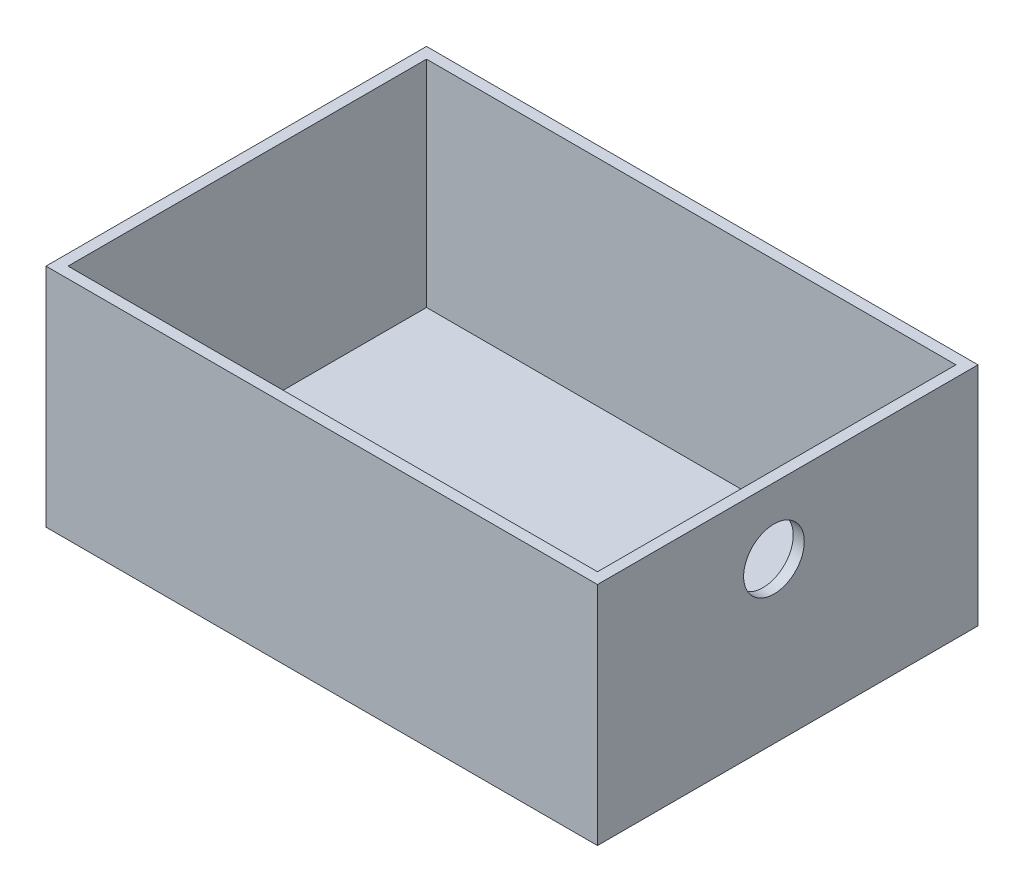
SolidWorks part; units mm, degrees
ref_plane "Front Plane" through (0, 0, 0) normal (0, 0, 1) x (1, 0, 0)
ref_plane "Top Plane" through (0, 0, 0) normal (0, 1, 0) x (1, 0, 0)
ref_plane "Right Plane" through (0, 0, 0) normal (1, 0, 0) x (0, 0, -1)
sketch "Sketch1" plane through (0, 0, 0) normal (0, 1, 0) x (1, 0, 0)
  line L1 (-50, -34.5) -> (50, -34.5)
  line L2 (-50, -34.5) -> (-50, 34.5)
  line L3 (-50, 34.5) -> (50, 34.5)
  line L4 (50, -34.5) -> (50, 34.5)
  line L5 (-50, -34.5) -> (50, 34.5) construction
  line L6 (-50, 34.5) -> (50, -34.5) construction
  point P0 (0, 0)
  dimension "D1" = 100
  dimension "D2" = 69
extrude "Boss-Extrude1" add sketch "Sketch1" along normal blind 41 contours L4 L3 L2 L1
sketch "Sketch3" plane through (0, 41, 0) normal (0, 1, 0) x (1, 0, 0)
  line L1 (-48, -32.5) -> (48, -32.5)
  line L2 (-48, -32.5) -> (-48, 32.5)
  line L3 (-48, 32.5) -> (48, 32.5)
  line L4 (48, -32.5) -> (48, 32.5)
  line L5 (-48, -32.5) -> (48, 32.5) construction
  line L6 (-48, 32.5) -> (48, -32.5) construction
  point P0 (0, 0)
  dimension "D1" = 96
  dimension "D2" = 65
extrude "Cut-Extrude2" cut sketch "Sketch3" against normal blind 39
sketch "Sketch4" plane through (0, 0, -34.5) normal (0, 0, -1) x (-1, 0, 0)
  line L0 (-50, 41) -> (-50, 0) construction
  line L1 (-48, 8) -> (-42, 8)
  line L2 (-48, 8) -> (-48, 2)
  line L3 (-48, 2) -> (-42, 2)
  line L4 (-42, 8) -> (-42, 2)
  line L5 (-48, 8) -> (-42, 2) construction
  line L6 (-48, 2) -> (-42, 8) construction
  line L7 (50, 0) -> (-50, 0) construction
  point P0 (-45, 5)
  dimension "D1" = 6
  dimension "D2" = 6
  dimension "D3" = 2
  dimension "D4" = 2
extrude "Cut-Extrude3" cut sketch "Sketch4" against normal blind 2
extrude "Boss-Extrude2" add sketch "Sketch1<4>" along normal blind 2
sketch "Sketch1<4>" plane through (0, 0, 0) normal (0, 1, 0) x (1, 0, 0) same geometry as "Sketch1"
sketch "Sketch6" plane through (50, 0, 0) normal (1, 0, 0) x (0, 0, -1)
  line L0 (-34.5, 41) -> (-34.5, 0) construction
  line L2 (-34.5, 0) -> (34.5, 0) construction
  circle A0 centre (-2.5, 29) radius 5.5
  dimension "D1" = 11
  dimension "D2" = 32
  dimension "D3" = 29
extrude "Cut-Extrude4" cut sketch "Sketch6" against normal blind 2
